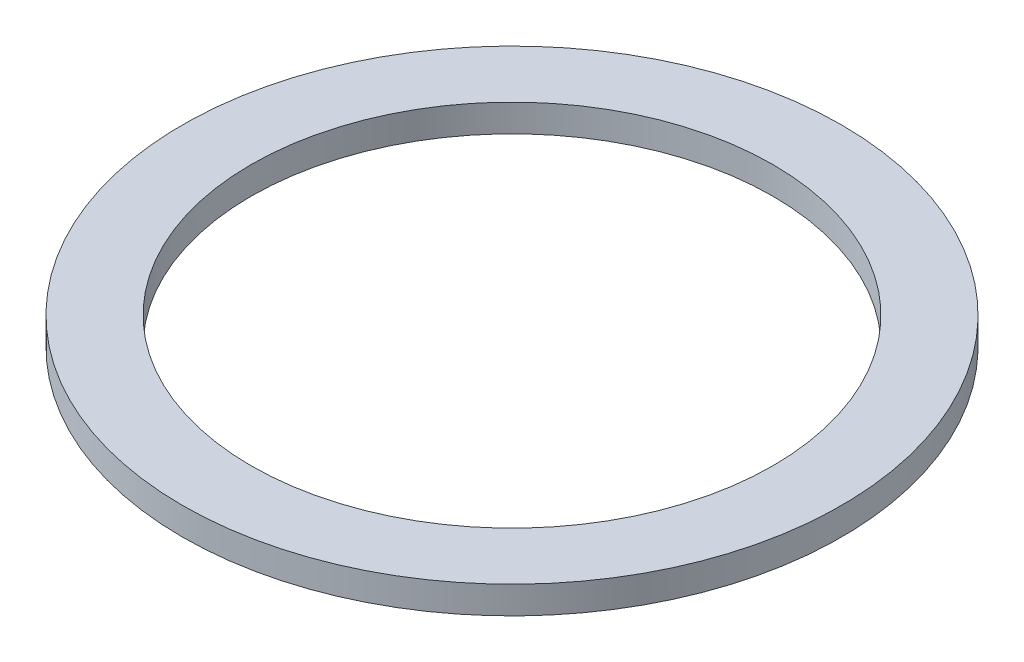
SolidWorks part; units mm, degrees
ref_plane "Front Plane" through (0, 0, 0) normal (0, 0, 1) x (1, 0, 0)
ref_plane "Top Plane" through (0, 0, 0) normal (0, 1, 0) x (1, 0, 0)
ref_plane "Right Plane" through (0, 0, 0) normal (1, 0, 0) x (0, 0, -1)
sketch "Sketch1" plane through (0, 0, 0) normal (0, 1, 0) x (1, 0, 0)
  circle A0 centre (0, 0) radius 60
  dimension "FLANGE_OD" = 120
extrude "Boss-Extrude1" add sketch "Sketch1" along normal blind 5
sketch "Sketch2" plane through (0, 0, 0) normal (0, 1, 0) x (1, 0, 0)
  circle A0 centre (0, 0) radius 47.5
  dimension "BORE_D" = 95
extrude "Cut-Extrude1" cut sketch "Sketch2" along normal through all
sketch "Sketch3" plane through (0, 5, 0) normal (0, 1, 0) x (1, 0, 0)
  circle A0 centre (0, 0) radius 28.0876 construction
  circle A1 centre (-28.0876, 0) radius 2.0052
  dimension "BOLT_D" = 4.0105
  dimension "BOLT_PCD" = 56.1752
extrude "Cut-Extrude2" cut sketch "Sketch3" against normal blind 3.732 rebuild error yes
pattern_circular "CirPattern1" count 8 over 360 rebuild error yes
